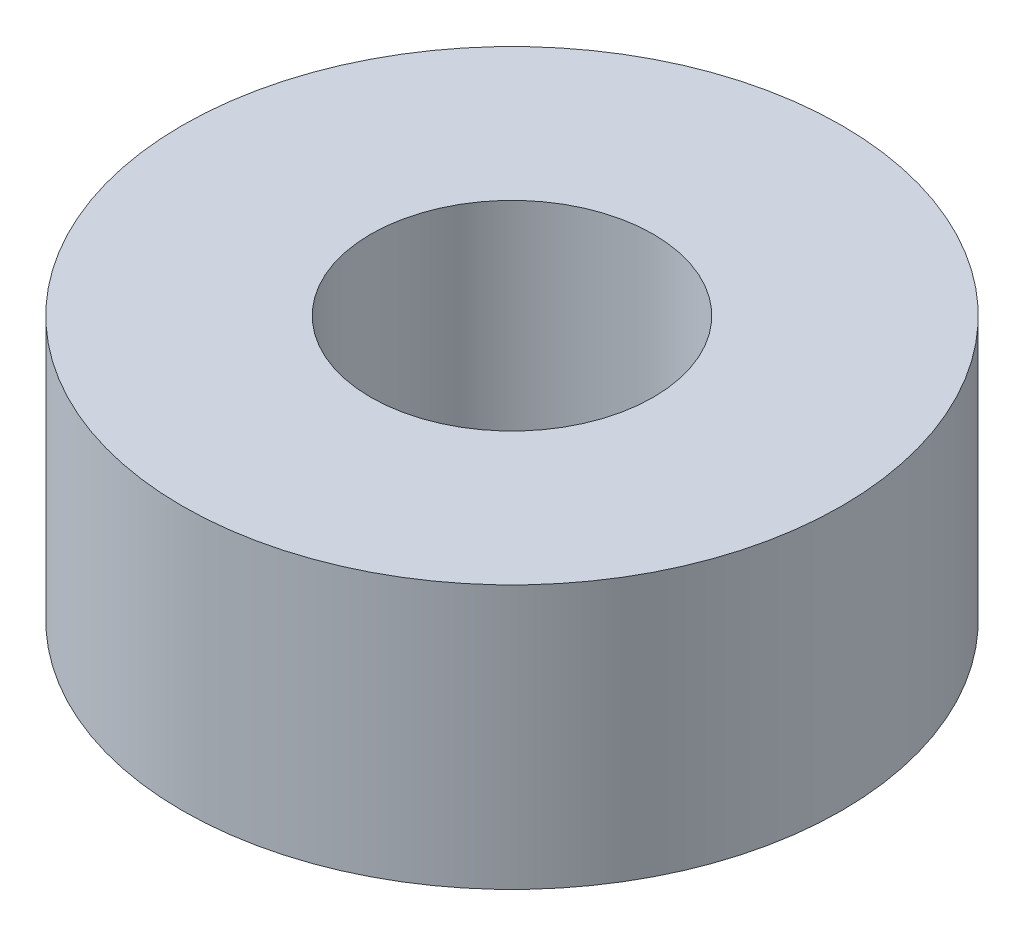
SolidWorks part; units mm, degrees
ref_plane "Front Plane" through (0, 0, 0) normal (0, 0, 1) x (1, 0, 0)
ref_plane "Top Plane" through (0, 0, 0) normal (0, 1, 0) x (1, 0, 0)
ref_plane "Right Plane" through (0, 0, 0) normal (1, 0, 0) x (0, 0, -1)
sketch "Sketch1" plane through (0, 0, 0) normal (0, 1, 0) x (1, 0, 0)
  circle A0 centre (0, 0) radius 17.5
  dimension "FLANGE_OD" = 35
extrude "Boss-Extrude1" add sketch "Sketch1" along normal blind 14
sketch "Sketch2" plane through (0, 0, 0) normal (0, 1, 0) x (1, 0, 0)
  circle A0 centre (0, 0) radius 7.5
  dimension "BORE_D" = 15
extrude "Cut-Extrude1" cut sketch "Sketch2" along normal through all
sketch "Sketch3" plane through (0, 14, 0) normal (0, 1, 0) x (1, 0, 0)
  circle A0 centre (0, 0) radius 5.1049 construction
  circle A1 centre (-5.1049, 0) radius 1.6703
  dimension "BOLT_D" = 3.3406
  dimension "BOLT_PCD" = 10.2097
extrude "Cut-Extrude2" cut sketch "Sketch3" against normal blind 8.7686 rebuild error yes
pattern_circular "CirPattern1" count 3 over 360 rebuild error yes
